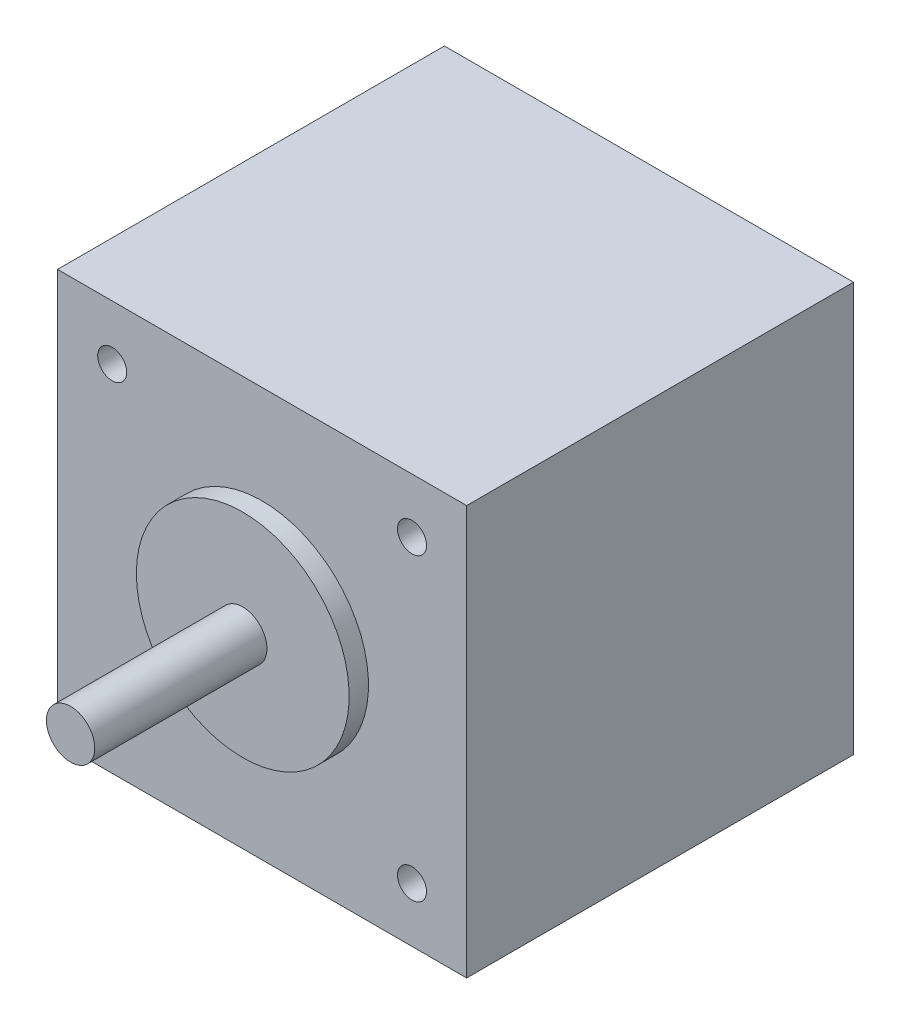
SolidWorks part; units mm, degrees
ref_plane "Спереди" through (0, 0, 0) normal (0, 0, 1) x (1, 0, 0)
ref_plane "Сверху" through (0, 0, 0) normal (0, 1, 0) x (1, 0, 0)
ref_plane "Справа" through (0, 0, 0) normal (1, 0, 0) x (0, 0, -1)
other "Configuration Table"
sketch "Эскиз1" plane through (0, 0, 0) normal (0, 0, 1) x (1, 0, 0)
  line L1 (-21.15, -21.15) -> (21.15, -21.15)
  line L2 (-21.15, -21.15) -> (-21.15, 21.15)
  line L3 (-21.15, 21.15) -> (21.15, 21.15)
  line L4 (21.15, -21.15) -> (21.15, 21.15)
  line L5 (-21.15, -21.15) -> (21.15, 21.15) construction
  line L6 (-21.15, 21.15) -> (21.15, -21.15) construction
  point P0 (0, 0)
  dimension "D1" = 42.3
  dimension "D2" = 42.3
extrude "Корпус" add sketch "Эскиз1" along normal blind 40
sketch "Эскиз2" plane through (0, 0, 0) normal (0, 0, 1) x (1, 0, 0)
  circle A0 centre (0, 0) radius 2.5
extrude "Вал_ПРЕДВ" add sketch "Эскиз2" along normal blind 59.8
sketch "Эскиз3" plane through (0, 0, 0) normal (0, 0, 1) x (1, 0, 0)
  circle A0 centre (0, 0) radius 11
  dimension "D1" = 22
extrude "Буртик_ПРЕДВ" add sketch "Эскиз3" along normal blind 42
sketch "Эскиз4" plane through (0, 0, 0) normal (0, 0, 1) x (1, 0, 0)
  circle A0 centre (0, 0) radius 8
  dimension "D1" = 16
sketch "Эскиз5" plane through (0, 0, 0) normal (0, 0, 1) x (1, 0, 0)
  circle A0 centre (-15.5, -15.5) radius 1.5
  circle A1 centre (-15.5, 15.5) radius 1.5
  circle A2 centre (15.5, -15.5) radius 1.5
  circle A3 centre (15.5, 15.5) radius 1.5
  dimension "D1" = 3
  dimension "D2" = 3
  dimension "D3" = 3
  dimension "D4" = 3
extrude "Крепеж_М3_ПРЕДВ" cut sketch "Эскиз5" against normal blind 4.5 from offset 40
equation "\"Мотор X ширина корпуса\"= 42.3"
equation "\"Мотор X высота корпуса\"= 42.3"
equation "\"Мотор X длина корпуса\"= 40"
equation "\"Мотор X вылет вала\"= 19.8"
equation "\"Мотор Y ширина корпуса\"= 42.3"
equation "\"Мотор Y высота корпуса\"= 42.3"
equation "\"Мотор Y длина корпуса\"= 48"
equation "\"Мотор Y вылет вала\"= 30"
equation "\"Мотор Z ширина корпуса\"= 42"
equation "\"Мотор Z высота корпуса\"= 42"
equation "\"Мотор Z длина корпуса\"= 40"
equation "\"Мотор Z вылет вала\"= 23"
equation "\"Мотор диаметр вала ПРЕДВ\"= 5"
equation "\"Мотор шаг крепления ПРЕДВ\"= 31"
equation "\"Мотор диаметр отверстий ПРЕДВ\"= 3"
equation "\"Мотор глубина отверстий ПРЕДВ\"= 4.5"
equation "\"Мотор диаметр буртика ПРЕДВ\"= 22"
equation "\"Мотор высота буртика ПРЕДВ\"= 2"
equation "\"Мотор диаметр шкива ПРЕДВ\"= 16"
equation "\"Мотор длина шкива ПРЕДВ\"= 12"
equation "\"Мотор отступ шкива ПРЕДВ\"= 5"
equation "\"Мотор X шаг градусов\"= 1.8"
equation "\"Мотор Y шаг градусов\"= 1.8"
equation "\"Мотор Z шаг градусов\"= 1.8"
equation "\"Мотор Y диаметр ротора\"= 25.78"
equation "\"D1@Эскиз1\" = \"Мотор X ширина корпуса\""
equation "\"D1@Корпус\" = \"Мотор X длина корпуса\""
equation "\"D1@Эскиз2\" = \"Мотор диаметр вала ПРЕДВ\""
equation "\"D1@Вал_ПРЕДВ\" = \"Мотор X длина корпуса\" + \"Мотор X вылет вала\""
equation "\"D1@Эскиз3\" = \"Мотор диаметр буртика ПРЕДВ\""
equation "\"D1@Буртик_ПРЕДВ\" = \"Мотор X длина корпуса\" + \"Мотор высота буртика ПРЕДВ\""
equation "\"D1@Эскиз4\" = \"Мотор диаметр шкива ПРЕДВ\""
equation "\"D1@Эскиз5\" = \"Мотор диаметр отверстий ПРЕДВ\""
equation "\"D2@Эскиз5\" = \"Мотор диаметр отверстий ПРЕДВ\""
equation "\"D3@Эскиз5\" = \"Мотор диаметр отверстий ПРЕДВ\""
equation "\"D4@Эскиз5\" = \"Мотор диаметр отверстий ПРЕДВ\""
equation "\"D1@Крепеж_М3_ПРЕДВ\" = \"Мотор глубина отверстий ПРЕДВ\""
equation "\"D19@Крепеж_М3_ПРЕДВ\" = \"Мотор X длина корпуса\""
equation "\"Ширина груза\"= 420"
equation "\"Глубина груза\"= 490"
equation "\"Высота груза\"= 297"
equation "\"Ширина ячейки\"= \"Ширина груза\" + 10"
equation "\"Глубина ячейки\"= \"Глубина груза\" + 10"
equation "\"Высота ячейки\"= \"Высота груза\" + 10 + 13"
equation "\"Колво ячеек ширина\"= 2"
equation "\"Колво ячеек высота\"= 2"
equation "\"Толщина стенки\" = \"Толщина тонких панелей\""
equation "\"Крепление дверцы\"= 5 "
equation "\"Ширина рейки\"= \"Толщина шестерни\""
equation "\"Высота рейки\"= 20"
equation "\"Высота пола\" = 2*\"Толщина тонких панелей\""
equation "\"Колво полозьев\"= 5"
equation "\"Отступ рейки\"= 20"
equation "\"Глубина каретки\"= \"Глубина ячейки\" + 30 + \"Мотор Y высота корпуса\" + 20"
equation "\"Отступ шпильки\"= 26"
equation "\"Диаметр шпильки\"= 5"
equation "\"Длинна шпильки\" = (\"Высота ячейки\"+\"Толщина горизонтальных плит\"+\"Высота пола\")*\"Колво ячеек высота\"+2*(\"Толщина горизонтальных плит\"+\"Отступ рейки\")"
equation "\"Ширина пластины\"= 50  "
equation "\"Высота зона выгрузки\"= \"Высота ячейки\" * 2 + \"Толщина стенки\" * 2"
equation "\"Колво выгрузки\"= 1"
equation "\"Отступ крепления мотора фиксации\" = (\"Ширина пластины\"+20-\"Толщина вертикальных стенок\")/2"
equation "\"Диаметр оси\"= 10"
equation "\"Диаметр ролика\"= 20"
equation "\"Колво роликов\"= 10"
equation "\"Шаг роликов\"= \"Диаметр ролика\" + 20"
equation "\"Ширина ячейки выгрузки\" = \"Ширина ячейки\"+\"Толщина вертикальных стенок\"+2*\"Отступ крепления мотора фиксации\""
equation "\"Длинна рейки\" = (\"Ширина ячейки\"+\"Толщина вертикальных стенок\"+\"Крепление дверцы\")*\"Колво ячеек ширина\"+\"Ширина ячейки выгрузки\"*\"Колво выгрузки\"+\"Толщина вертикальных стенок\"+2*\"Отступ крепления мотора фиксации\"-\"Крепление дверцы\"*\"Колво ячеек ширина\""
equation "\"Толщина шестерни\"= 10"
equation "\"Толщина тонких панелей\"= 6"
equation "\"Толщина вертикальных стенок\"= 18"
equation "\"Толщина горизонтальных плит\"= 18"
equation "\"Базовая высота корпуса\"= (\"Высота ячейки\"+\"Толщина тонких панелей\"+\"Высота пола\")*\"Колво ячеек высота\"+6*\"Толщина тонких панелей\"+\"Мотор X ширина корпуса\"+\"Мотор Y ширина корпуса\"+75"
equation "\"Высота корпуса\"= (\"Высота ячейки\"+\"Толщина горизонтальных плит\"+\"Высота пола\")*\"Колво ячеек высота\"+2*\"Толщина горизонтальных плит\"+4*\"Толщина тонких панелей\"+\"Мотор X ширина корпуса\"+\"Мотор Y ширина корпуса\"+75"
equation "\"Смещение центра корпуса\"= (\"Высота корпуса\"-\"Базовая высота корпуса\")/2-(\"Толщина горизонтальных плит\"-\"Толщина тонких панелей\")"
equation "\"Отметка пола\"= -\"Базовая высота корпуса\"/2+\"Толщина тонких панелей\""
equation "\"Отметка потолка\"= \"Отметка пола\"+\"Высота корпуса\"-2*\"Толщина горизонтальных плит\""
equation "\"Отметка верхней полки\"= \"Отметка потолка\"-(28+\"Толщина тонких панелей\")-\"Высота ячейки\"-\"Высота пола\""
equation "\"Отметка нижней полки\"= \"Отметка верхней полки\"-\"Высота ячейки\"-\"Высота пола\"-\"Толщина горизонтальных плит\""
